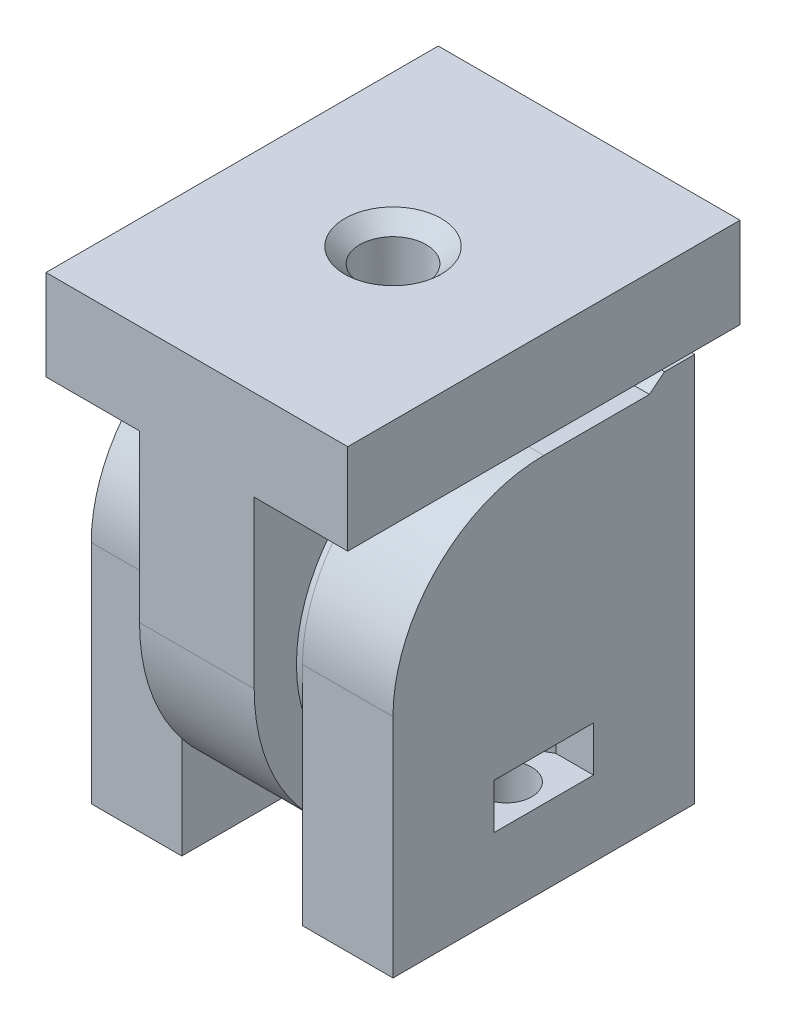
SolidWorks part; units mm, degrees
ref_plane "Front Plane" through (0, 0, 0) normal (0, 0, 1) x (1, 0, 0)
ref_plane "Top Plane" through (0, 0, 0) normal (0, 1, 0) x (1, 0, 0)
ref_plane "Right Plane" through (0, 0, 0) normal (1, 0, 0) x (0, 0, -1)
sketch "Sketch1" plane through (0, 0, 0) normal (1, 0, 0) x (0, 0, -1)
  circle A0 centre (0, 0) radius 10
  dimension "D1" = 20
extrude "Boss-Extrude1" add sketch "Sketch1" along normal blind 20
sketch "Sketch2" plane through (20, 0, 0) normal (1, 0, 0) x (0, 0, -1)
  line L5 (-10, 10) -> (10, 10)
  line L6 (-10, 10) -> (-10, -15)
  line L7 (-10, -15) -> (10, -15)
  line L8 (10, 10) -> (10, -15)
  circle A0 centre (0, 0) radius 10 construction
  point P0 (0, 0)
  point P6 (11.7696, -19.9449)
  point P7 (0, 10)
  point P10 (10, -14.5972)
  dimension "D1" = 15
extrude "Boss-Extrude2" add sketch "Sketch2" against normal blind 6
fillet "Fillet1" radius 10 1 edges at (17, 10, 10)
ref_plane "Plane3" through (10, 0, 0) normal (-1, 0, 0) x (0, 0, 1)
mirror "Mirror2" about plane through (10, 0, 0) normal (-1, 0, 0) of "Boss-Extrude2"
fillet "Fillet2" radius 10 1 edges at (3, 10, 10)
sketch "Sketch3" plane through (0, 10, 0) normal (0, 1, 0) x (1, 0, 0)
  line L0 (6, 10) -> (0, 10) construction
  line L1 (14, 10) -> (20, 10) construction
  circle A0 centre (3, 0) radius 1.7
  circle A1 centre (17, 0) radius 1.7
  point P6 (0, 0)
  point P9 (17, 10)
  point P10 (3, 10)
  dimension "D1" = 3.4
  dimension "D2" = 10
sketch "Sketch5" plane through (14, 0, 0) normal (-1, 0, 0) x (0, 0, 1)
  line L0 (13, 0) -> (13, 17)
  line L1 (13, 17) -> (-13, 17)
  line L2 (-10, 10) -> (0, 10) construction
  line L3 (-13, 0) -> (-13, 17)
  circle A0 centre (0, 0) radius 10.2
  circle A1 centre (0, 0) radius 10 construction
  circle A2 centre (0, 0) radius 13
  point P9 (13, 16.8825)
  line M5 (10, -15) -> (10, 0)
  line M15 (-10, 0) -> (-10, -15)
  dimension "D1" = 0.2
  dimension "D2" = 26
  dimension "D3" = 7
extrude "Boss-Extrude3" add sketch "Sketch5" along normal offset from surface (7.6 mm away) 0.2 from offset 0.2 separate body contours A2 A0 M15 M5 | A2 A0 M15 M5 | A2 L0 L1 L3 region at (14, 13.3106, 0) region at (14, -4.3017, 11.9109) region at (14, -12.7718, 0) up to face at (6, -10, 0)
sketch "Sketch6" plane through (6.2, 0, 0) normal (-1, 0, 0) x (0, 0, 1)
  line L1 (13, 17) -> (-13, 17)
  line L2 (13, 17) -> (13, 11)
  line L3 (13, 11) -> (-13, 11)
  line L4 (-13, 17) -> (-13, 11)
  line L5 (-10, 10) -> (0, 10) construction
  line L7 (13, 17) -> (-13, 17) construction
  point P5 (-10.0218, 10.4)
  point P6 (-12.9171, 17)
  point P11 (-13, 17)
  dimension "D1" = 1
extrude "Boss-Extrude4" add sketch "Sketch6" along normal up to surface (6.2 mm away) contours L2 L1 L4 L3 up to face at (0, -1.5858, 0.4142)
sketch "Sketch7" plane through (13.8, 0, 0) normal (1, 0, 0) x (0, 0, -1)
  line L0 (-13, 0) -> (-13, 17) construction
  line L1 (13, 17) -> (-13, 17)
  line L2 (13, 17) -> (13, 11)
  line L3 (13, 11) -> (-13, 11)
  line L4 (-13, 17) -> (-13, 11)
  line L5 (10, 10) -> (0, 10) construction
  dimension "D1" = 1
extrude "Boss-Extrude5" add sketch "Sketch7" along normal up to surface (6.2 mm away) up to face at (20, -1.5858, 0.4142)
sketch "Sketch8" plane through (20, 0, 0) normal (1, 0, 0) x (0, 0, -1)
  line L0 (13, 17) -> (-13, 17) construction
  circle A0 centre (0, 14) radius 1.7
  point P2 (0, 0)
  dimension "D1" = 3.4
  dimension "D2" = 3
sketch "Sketch10" plane through (0, 17, 0) normal (0, 1, 0) x (1, 0, 0)
  line L0 (10, 11) -> (10, -11) construction
  line L1 (0, 13) -> (0, -13) construction
  circle A0 centre (10, 0) radius 2.2
  point P4 (0, 0)
  point P7 (0, 0)
  dimension "D1" = 4.4
extrude "Cut-Extrude6" cut sketch "Sketch10" against normal blind 7
chamfer "Chamfer2" distance 1 angle 45 1 edges at (10, 17, 2.2)
sketch "Sketch11" plane through (0, -15, 0) normal (0, -1, 0) x (-1, 0, 0)
  line L0 (-2.5, 0) -> (-10, 0)
  line L1 (-10, -11) -> (-10, 11) construction
  line L2 (-17.5, 0) -> (-10, 0)
  line L3 (-6, -10) -> (0, -10) construction
  circle A0 centre (-2.5, 0) radius 1.7
  circle A1 centre (-17.5, 0) radius 1.7
  dimension "D1" = 3.4
  dimension "D2" = 15
  dimension "D3" = 10
extrude "Cut-Extrude7" cut sketch "Sketch11" against normal blind 20 contours A0 | A1 region at (19.1519, -15, 0) region at (2.5, -15, -1.6519)
sketch "Sketch12" plane through (0, -15, 0) normal (0, -1, 0) x (-1, 0, 0)
  line L0 (-17.5, -3.2909) -> (-20, -3.2909)
  line L1 (-14.65, -1.6454) -> (-14.65, 1.6454)
  line L2 (-14.65, 1.6454) -> (-17.5, 3.2909)
  line L3 (-17.5, 3.2909) -> (-20.35, 1.6454)
  line L4 (-20.35, 1.6454) -> (-20.35, -1.6454)
  line L5 (-20.35, -1.6454) -> (-17.5, -3.2909)
  line L6 (-17.5, -3.2909) -> (-14.65, -1.6454)
  line L7 (-20, -10) -> (-20, 10) construction
  line L8 (-20, -3.2909) -> (-20, 3.2909)
  line L9 (-20, 1.7) -> (-20, -1.7) construction
  line L10 (-20, 3.2909) -> (-17.5, 3.2909)
  line L11 (-10, -11) -> (-10, 11) construction
  line L12 (0, 3.2909) -> (-2.5, 3.2909)
  line L13 (0, -3.2909) -> (0, 3.2909)
  line L14 (-2.5, -3.2909) -> (-5.35, -1.6454)
  line L15 (0.35, -1.6454) -> (-2.5, -3.2909)
  line L16 (0.35, 1.6454) -> (0.35, -1.6454)
  line L17 (-2.5, 3.2909) -> (0.35, 1.6454)
  line L18 (-5.35, 1.6454) -> (-2.5, 3.2909)
  line L19 (-5.35, -1.6454) -> (-5.35, 1.6454)
  line L20 (-2.5, -3.2909) -> (0, -3.2909)
  circle A0 centre (-17.5, 0) radius 2.85 construction
  circle A1 centre (-2.5, 0) radius 2.85 construction
  circle M7 centre (-2.5, 0) radius 1.7
  line M8 (0, -10) -> (0, 10)
  dimension "D1" = 5.7
extrude "Cut-Extrude8" cut sketch "Sketch12" against normal blind 3 from offset 5 contours L19 L14 L15 L13 L17 L18 M7 | M7 | L15 L20 M8 | L12 L17 M8 | L8 L5 L6 L1 L2 L3 | L8 L0 L5 | L10 L8 L3 region at (19.1667, -15, 2.8098) region at (17.3786, -15, 0) region at (19.1667, -15, -2.8098) region at (0.8333, -15, -2.8098) region at (1.2924, -15, -2.4958) region at (0.8333, -15, 2.8098) region at (2.5, -15, 0) offset against normal yes
sketch "Sketch13" plane through (20, 0, 0) normal (1, 0, 0) x (0, 0, -1)
  line L0 (10, 10) -> (10, 10.8)
  line L1 (10, 10.8) -> (8, 10.8)
  line L2 (8, 10.8) -> (7, 10)
  line L3 (10, 10) -> (0, 10) construction
  line L4 (-13, 11) -> (13, 11) construction
  line L5 (7, 10) -> (10, 10)
  dimension "D1" = 0.2
  dimension "D2" = 2
  dimension "D3" = 3
extrude "Boss-Extrude6" add sketch "Sketch13" against normal up to surface (6 mm away) up to face at (14, 7.357, -7.357)
sketch "Sketch15" plane through (0, 0, 0) normal (-1, 0, 0) x (0, 0, 1)
  line L0 (-10, 10) -> (-10, 10.8)
  line L1 (-10, 10.8) -> (-8, 10.8)
  line L2 (-8, 10.8) -> (-7, 10)
  line L3 (-10, 10) -> (0, 10) construction
  line L4 (-7, 10) -> (-10, 10)
  line L5 (-13, 11) -> (13, 11) construction
  dimension "D1" = 0.2
  dimension "D2" = 2
  dimension "D3" = 3
extrude "Boss-Extrude7" add sketch "Sketch15" against normal up to surface (6 mm away) up to face at (6, -10, 0)
